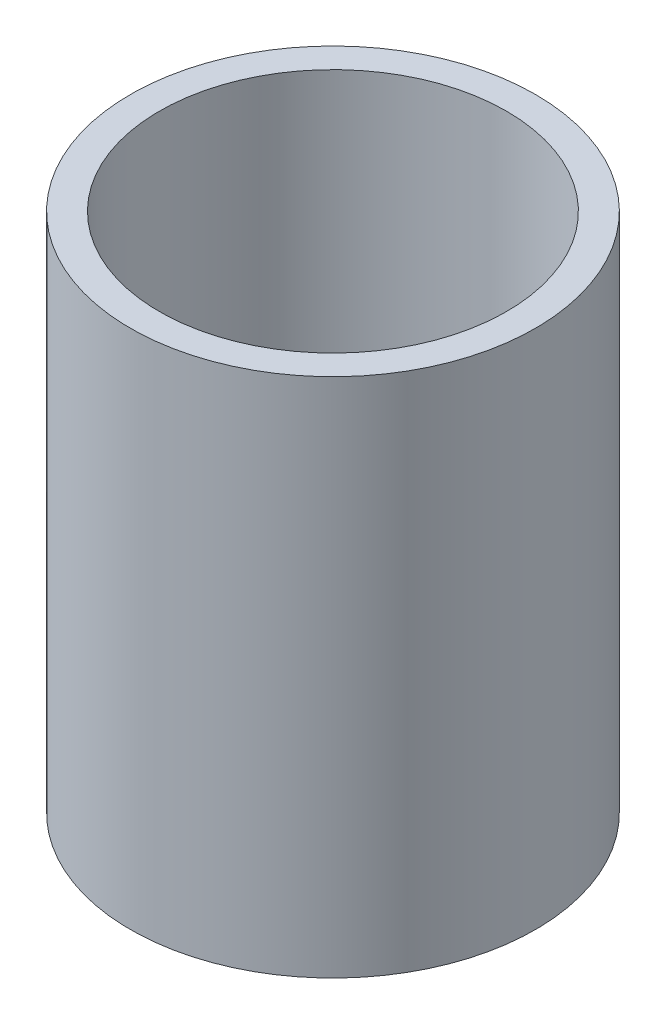
SolidWorks part; units mm, degrees
ref_plane "Front Plane" through (0, 0, 0) normal (0, 0, 1) x (1, 0, 0)
ref_plane "Top Plane" through (0, 0, 0) normal (0, 1, 0) x (1, 0, 0)
ref_plane "Right Plane" through (0, 0, 0) normal (1, 0, 0) x (0, 0, -1)
sketch "Sketch1" plane through (0, 0, 0) normal (0, 1, 0) x (1, 0, 0)
  circle A0 centre (0, 0.545) radius 15
  circle A1 centre (0, 0.545) radius 17.5
  dimension "D1" = 30
  dimension "D2" = 35
extrude "Boss-Extrude1" add sketch "Sketch1" along normal blind 45
